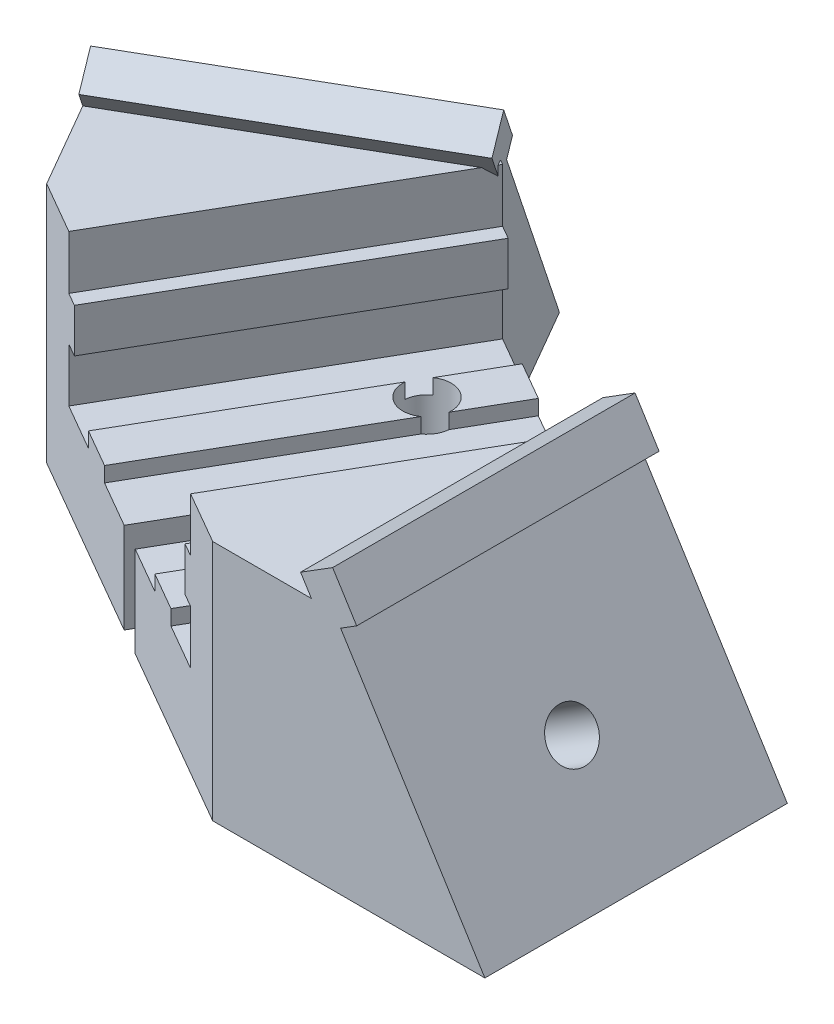
SolidWorks part; units mm, degrees
ref_plane "Front Plane" through (0, 0, 0) normal (0, 0, 1) x (1, 0, 0)
ref_plane "Top Plane" through (0, 0, 0) normal (0, 1, 0) x (1, 0, 0)
ref_plane "Right Plane" through (0, 0, 0) normal (1, 0, 0) x (0, 0, -1)
sketch "Esquisse1" plane through (0, 0, 0) normal (0, 0, 1) x (1, 0, 0)
  line L0 (8, 16) -> (17.9979, 0)
  line L1 (17.9979, 0) -> (0, 0)
  line L2 (0, 0) -> (0, 16)
  line L3 (0, 16) -> (8, 16)
  dimension "D1" = 8
  dimension "D2" = 122
  dimension "D3" = 16
extrude "Main" add sketch "Esquisse1" along normal blind 20
sketch "Esquisse2" plane through (12.9438, 8.0882, 0) normal (0.848, 0.5299, 0) x (0, 0, -1)
  line L0 (-20, -9.5374) -> (0, -9.5374) construction
  line L3 (-20, -9.5374) -> (-20, 9.3294) construction
  circle A0 centre (-10, -1.5374) radius 1.6
  dimension "D1" = 3.2
  dimension "D2" = 8
  dimension "D3" = 10
extrude "HoleForLauncherFixing" cut sketch "Esquisse2" against normal through all
ref_plane "Plan1" through (8.7036, 5.4386, 0) normal (0.848, 0.5299, 0) x (0, 0, -1)
ref_axis "Axe1" through (4.525, 12.1258, 0) along (0.5299, -0.848, 0)
ref_plane "Plan3" through (0, 0, 0) normal (-0.866, 0, -0.5) x (0, -1, 0)
sketch "Esquisse4" plane through (0, 0, 0) normal (-0.866, 0, -0.5) x (0, -1, 0)
  line L1 (4.4994, 17.8157) -> (-17.7877, 17.8157)
  line L2 (4.4994, 17.8157) -> (4.4994, -17.0003)
  line L3 (4.4994, -17.0003) -> (-17.7877, -17.0003)
  line L4 (-17.7877, 17.8157) -> (-17.7877, -17.0003)
extrude "Enlèv. mat.-Extru.3" cut sketch "Esquisse4" against normal blind 6
ref_plane "Plan4" through (1.7321, 0, -3) normal (-0.5, 0, 0.866) x (0, 1, 0)
ref_plane "Plan5" through (0, 0, 12) normal (0.5, 0, -0.866) x (-0.866, 0, -0.5)
ref_plane "Plan6" through (-8.6603, 0, 15) normal (0.5, 0, -0.866) x (-0.866, 0, -0.5)
sketch "Esquisse5" plane through (-3.4641, 0, 18) normal (0.5, 0, -0.866) x (-0.866, 0, -0.5)
  line L0 (-4, 0) -> (10, 0)
  line L1 (10, 0) -> (10, 6)
  line L2 (10, 6) -> (6.45, 6)
  line L3 (6.45, 6) -> (6.45, 7)
  line L4 (6.45, 7) -> (3.55, 7)
  line L5 (3.55, 7) -> (3.55, 6)
  line L6 (3.55, 6) -> (0, 6)
  line L7 (0, 6) -> (0, 9.55)
  line L8 (0, 9.55) -> (1, 9.55)
  line L9 (1, 9.55) -> (1, 12.45)
  line L10 (1, 12.45) -> (0, 12.45)
  line L11 (0, 12.45) -> (0, 16)
  line L12 (0, 16) -> (-4, 16)
  line L13 (-4, 16) -> (-4, 0)
  dimension "D1" = 10
  dimension "D2" = 2.9
  dimension "D3" = 1
  dimension "D4" = 6
  dimension "D5" = 4
  dimension "D6" = 10
extrude "MakerBeanFixing" add sketch "Esquisse5" along normal blind 21
sketch "Esquisse6" plane through (12.9438, 8.0882, 0) normal (0.848, 0.5299, 0) x (0, 0, -1)
  line L0 (0, -9.5374) -> (0, 9.3294) construction
  line L1 (0, 8.4626) -> (-20, 8.4626)
  line L2 (0, 8.4626) -> (0, 11.4626)
  line L3 (0, 11.4626) -> (-20, 11.4626)
  line L4 (-20, 8.4626) -> (-20, 11.4626)
  line L5 (-20, -9.5374) -> (0, -9.5374) construction
  dimension "D1" = 18
  dimension "D2" = 3
extrude "AntiRotationSystem" add sketch "Esquisse6" along normal mid plane 2.5
sketch "Esquisse7" plane through (0, 7, 0) normal (0, 1, 0) x (1, 0, 0)
  line L2 (1.45, 3.4115) -> (3.9615, 1.9615) construction
  line L3 (3.9615, 1.9615) -> (-6.5385, -16.225) construction
  circle A0 centre (0.2058, -1.6436) radius 1.6
  dimension "D1" = 3.2
  dimension "D2" = 5
  dimension "D3" = 1.45
extrude "TopMakerBeanFixingHole" cut sketch "Esquisse7" against normal through all
sketch "Esquisse8" plane through (0, 0, 0) normal (0, 0, -1) x (-1, 0, 0)
  line L0 (-8.4594, 15.2649) -> (-17.9979, 0)
  line L1 (-17.9979, 0) -> (-8.4594, 15.2649) construction
  line L2 (-17.9979, 0) -> (-21.6021, 2.2522)
  line L3 (-21.6021, 2.2522) -> (-10.4738, 20.0612)
  line L4 (-8.4594, 15.2649) -> (-9.5194, 15.9273)
  line L6 (-17.9979, 0) -> (-8.4594, 15.2649) construction
  line L9 (-9.5194, 15.9273) -> (-7.9297, 18.4714)
  line L10 (-7.9297, 18.4714) -> (-10.4738, 20.0612)
  dimension "D1" = 3
extrude "Enlèv. mat.-Extru.4" cut sketch "Esquisse8" against normal through all
sketch "Esquisse3" plane through (8.7036, 5.4386, 0) normal (0.848, 0.5299, 0) x (0, 0, -1)
  circle A0 centre (-10, -1.5374) radius 4.25
  circle A1 centre (-10, -1.5374) radius 1.6 construction
  dimension "D1" = 8.5
extrude "BigHoleForLauncherFixing" cut sketch "Esquisse3" against normal through all
ref_plane "Plane1" through (-4.3301, 0, -2.5) normal (-0.866, 0, -0.5) x (0, -1, 0)
mirror "Mirror1" about plane through (-4.3301, 0, -2.5) normal (-0.866, 0, -0.5) of bodies 103
